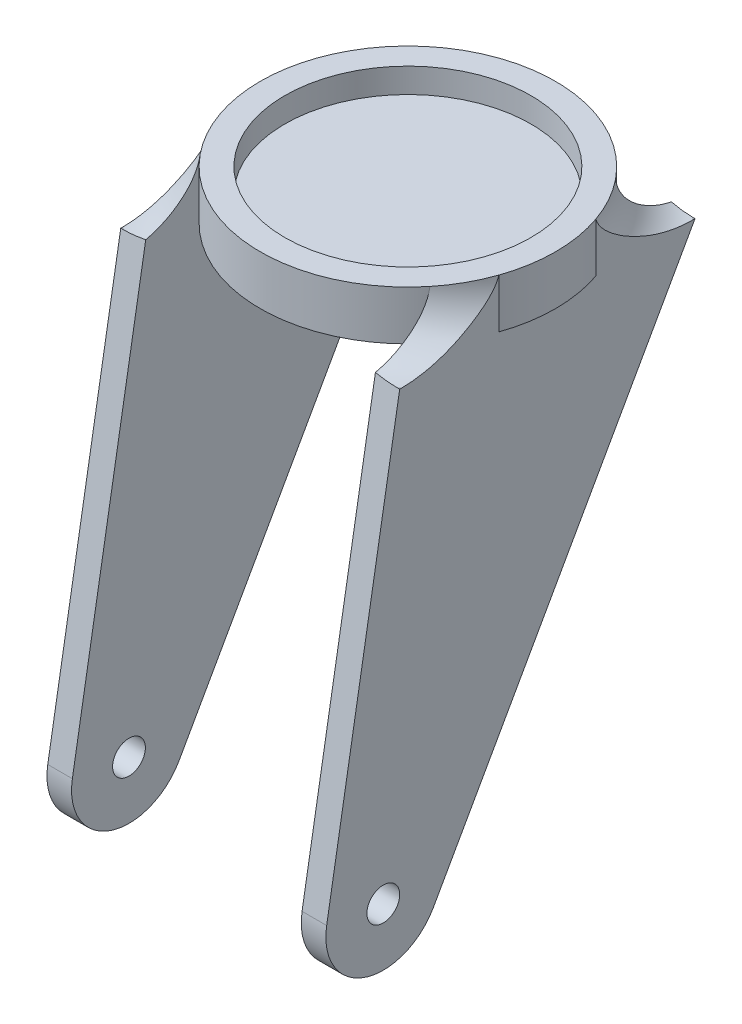
SolidWorks part; units mm, degrees
ref_plane "Plan de face" through (0, 0, 0) normal (0, 0, 1) x (1, 0, 0)
ref_plane "Plan de dessus" through (0, 0, 0) normal (0, 1, 0) x (1, 0, 0)
ref_plane "Plan de droite" through (0, 0, 0) normal (1, 0, 0) x (0, 0, -1)
sketch "Esquisse1" plane through (0, 0, 0) normal (0, 1, 0) x (1, 0, 0)
  circle A0 centre (0, 0) radius 15
  circle A1 centre (0, 0) radius 18
  dimension "D1" = 30
  dimension "D2" = 3
extrude "Boss.-Extru.1" add sketch "Esquisse1" along normal blind 3
sketch "Esquisse3" plane through (0, 0, 0) normal (0, -1, 0) x (1, 0, 0)
  circle A0 centre (0, 0) radius 18
extrude "Boss.-Extru.3" add sketch "Esquisse3" along normal blind 3
sketch "Esquisse2" plane through (0, 0, 0) normal (1, 0, 0) x (0, 0, -1)
  line L1 (-18, -3) -> (-26.9003, -55.1729)
  line L5 (18, 3) -> (-18, 3) construction
  line L6 (18, -3) -> (-13.8971, -59.7785)
  line L7 (-18, -3) -> (18, -3)
  arc A0 (-26.9003, -55.1729) -> (-13.8971, -59.7785) centre (-20, -56.35) ccw
  circle A1 centre (-20, -56.35) radius 2
  dimension "D2" = 7
  dimension "D5" = 4
  dimension "D1" = 20
  dimension "D6" = 59.35
extrude "Boss.-Extru.2" add sketch "Esquisse2" along normal blind 3 from offset 14
mirror "Symétrie1" about plane through (0, 0, 0) normal (1, 0, 0) of "Boss.-Extru.2"
fillet "Fillet1" radius 6.6 4 edges at (-15.7332, -3, -8.7445) (-15.7332, -3, 8.7445) (15.7332, -3, -8.7445) (15.7332, -3, 8.7445)
